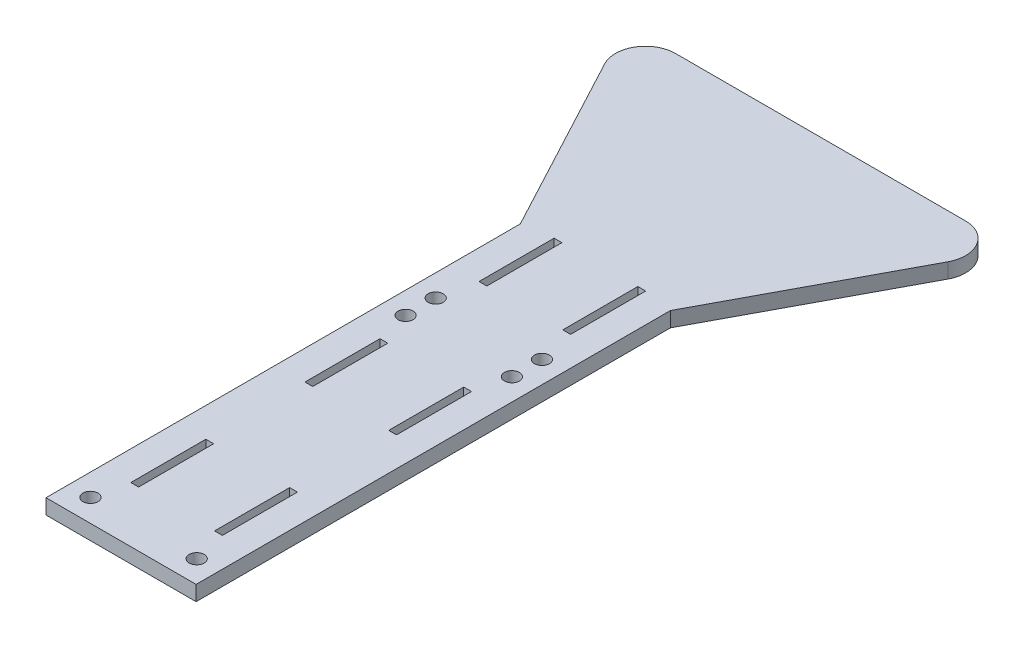
SolidWorks part; units mm, degrees
material "PC High Viscosity"
ref_plane "Front" through (0, 0, 0) normal (0, 0, 1) x (1, 0, 0)
ref_plane "Top" through (0, 0, 0) normal (0, 1, 0) x (1, 0, 0)
ref_plane "Right" through (0, 0, 0) normal (1, 0, 0) x (0, 0, -1)
sketch "Sketch1" plane through (0, 0, 0) normal (0, 1, 0) x (1, 0, 0)
  line L0 (-31.75, 0) -> (31.75, 0)
  line L1 (31.75, 0) -> (31.75, 200.66)
  line L2 (31.75, 200.66) -> (82.55, 295.91)
  line L3 (82.55, 295.91) -> (-82.55, 295.91)
  line L4 (-82.55, 295.91) -> (-31.75, 200.66)
  line L5 (-31.75, 200.66) -> (-31.75, 0)
  point P4 (0, 0)
  dimension "D1" = 63.5
  dimension "D2" = 200.66
  dimension "D3" = 95.25
  dimension "D4" = 165.1
extrude "Boss-Extrude1" add sketch "Sketch1" along normal blind 6.35
sketch "Sketch2" plane through (0, 6.35, 0) normal (0, 1, 0) x (1, 0, 0)
  line L0 (-19.304, 199.39) -> (-19.304, 173.99) construction
  line L1 (-19.304, 173.99) -> (-16.129, 173.99) construction
  line L2 (-16.129, 173.99) -> (-16.129, 199.39) construction
  line L3 (-16.129, 199.39) -> (-19.304, 199.39) construction
  line L4 (-19.304, 125.73) -> (-19.304, 100.33) construction
  line L5 (-19.304, 100.33) -> (-16.129, 100.33) construction
  line L6 (-16.129, 100.33) -> (-16.129, 125.73) construction
  line L7 (-16.129, 125.73) -> (-19.304, 125.73) construction
  line L12 (-19.304, 52.07) -> (-19.304, 26.67) construction
  line L13 (-19.304, 26.67) -> (-16.129, 26.67) construction
  line L14 (-16.129, 26.67) -> (-16.129, 52.07) construction
  line L15 (-16.129, 52.07) -> (-19.304, 52.07) construction
  line L20 (-19.304, 199.39) -> (-19.304, 173.99) construction
  line L21 (-19.304, 173.99) -> (-16.129, 173.99) construction
  line L22 (-16.129, 173.99) -> (-16.129, 199.39) construction
  line L23 (-16.129, 199.39) -> (-19.304, 199.39) construction
  line L24 (-19.304, 125.73) -> (-19.304, 100.33) construction
  line L25 (-19.304, 100.33) -> (-16.129, 100.33) construction
  line L26 (-16.129, 100.33) -> (-16.129, 125.73) construction
  line L27 (-16.129, 125.73) -> (-19.304, 125.73) construction
  line L32 (-19.304, 52.07) -> (-19.304, 26.67) construction
  line L33 (-19.304, 26.67) -> (-16.129, 26.67) construction
  line L34 (-16.129, 26.67) -> (-16.129, 52.07) construction
  line L35 (-16.129, 52.07) -> (-19.304, 52.07) construction
  line L36 (16.129, 52.07) -> (16.129, 26.67) construction
  line L37 (16.129, 26.67) -> (19.304, 26.67) construction
  line L38 (19.304, 26.67) -> (19.304, 52.07) construction
  line L39 (19.304, 52.07) -> (16.129, 52.07) construction
  line L44 (16.129, 125.73) -> (16.129, 100.33) construction
  line L45 (16.129, 100.33) -> (19.304, 100.33) construction
  line L46 (19.304, 100.33) -> (19.304, 125.73) construction
  line L47 (19.304, 125.73) -> (16.129, 125.73) construction
  line L48 (16.129, 199.39) -> (16.129, 173.99) construction
  line L49 (16.129, 173.99) -> (19.304, 173.99) construction
  line L50 (19.304, 173.99) -> (19.304, 199.39) construction
  line L51 (19.304, 199.39) -> (16.129, 199.39) construction
  line L56 (16.129, 52.07) -> (16.129, 26.67) construction
  line L57 (16.129, 26.67) -> (19.304, 26.67) construction
  line L58 (19.304, 26.67) -> (19.304, 52.07) construction
  line L59 (19.304, 52.07) -> (16.129, 52.07) construction
  line L60 (16.129, 125.73) -> (16.129, 100.33) construction
  line L61 (16.129, 100.33) -> (19.304, 100.33) construction
  line L62 (19.304, 100.33) -> (19.304, 125.73) construction
  line L63 (19.304, 125.73) -> (16.129, 125.73) construction
  line L68 (16.129, 199.39) -> (16.129, 173.99) construction
  line L69 (16.129, 173.99) -> (19.304, 173.99) construction
  line L70 (19.304, 173.99) -> (19.304, 199.39) construction
  line L71 (19.304, 199.39) -> (16.129, 199.39) construction
  line L72 (-19.3675, 23.495) -> (-19.304, 26.67) construction
  line L73 (-19.3675, 23.495) -> (-16.0655, 23.495)
  line L74 (-19.3675, 23.495) -> (-19.3675, 55.245)
  line L75 (-19.3675, 55.245) -> (-16.0655, 55.245)
  line L76 (-16.0655, 23.495) -> (-16.0655, 55.245)
  line L77 (-19.3675, 97.155) -> (-16.0655, 97.155)
  line L78 (-19.3675, 97.155) -> (-19.3675, 128.905)
  line L79 (-19.3675, 128.905) -> (-16.0655, 128.905)
  line L80 (-16.0655, 97.155) -> (-16.0655, 128.905)
  line L81 (-19.3675, 170.815) -> (-16.0655, 170.815)
  line L82 (-19.3675, 170.815) -> (-19.3675, 202.565)
  line L83 (-19.3675, 202.565) -> (-16.0655, 202.565)
  line L84 (-16.0655, 170.815) -> (-16.0655, 202.565)
  line L85 (16.0655, 23.495) -> (19.3675, 23.495)
  line L86 (16.0655, 23.495) -> (16.0655, 55.245)
  line L87 (16.0655, 55.245) -> (19.3675, 55.245)
  line L88 (19.3675, 23.495) -> (19.3675, 55.245)
  line L89 (16.0655, 97.155) -> (19.3675, 97.155)
  line L90 (16.0655, 97.155) -> (16.0655, 128.905)
  line L91 (16.0655, 128.905) -> (19.3675, 128.905)
  line L92 (19.3675, 97.155) -> (19.3675, 128.905)
  line L93 (16.0655, 170.815) -> (19.3675, 170.815)
  line L94 (16.0655, 170.815) -> (16.0655, 202.565)
  line L95 (16.0655, 202.565) -> (19.3675, 202.565)
  line L96 (19.3675, 170.815) -> (19.3675, 202.565)
  line L97 (-16.129, 52.07) -> (-16.0655, 55.245) construction
  line L98 (-19.3675, 97.155) -> (-19.304, 100.33) construction
  line L99 (-16.129, 125.73) -> (-16.0655, 128.905) construction
  line L100 (-19.304, 173.99) -> (-19.3675, 170.815) construction
  line L101 (-16.129, 199.39) -> (-16.0655, 202.565) construction
  line L102 (16.129, 199.39) -> (16.0655, 202.565) construction
  line L103 (19.304, 173.99) -> (19.3675, 170.815) construction
  line L104 (16.129, 125.73) -> (16.0655, 128.905) construction
  line L105 (19.304, 100.33) -> (19.3675, 97.155) construction
  line L106 (16.129, 52.07) -> (16.0655, 55.245) construction
  line L107 (19.304, 26.67) -> (19.3675, 23.495) construction
  dimension "D1" = 3.302
  dimension "D2" = 31.75
extrude "Cut-Extrude1" cut sketch "Sketch2" against normal through all
sketch "Sketch3" plane through (0, 6.35, 0) normal (0, 1, 0) x (1, 0, 0)
  line L0 (0, 295.91) -> (0, 149.225) construction
  line L1 (82.55, 295.91) -> (-82.55, 295.91) construction
  line L2 (0, 149.225) -> (-31.75, 149.225) construction
  line L3 (-31.75, 200.66) -> (-31.75, 0) construction
  line L6 (-19.304, 128.27) -> (-19.304, 171.45) construction
  line L9 (-31.75, 0) -> (31.75, 0) construction
  circle A0 centre (-22.479, 155.575) radius 3.175
  circle A1 centre (-22.479, 142.875) radius 3.175
  circle A2 centre (22.479, 142.875) radius 3.175
  circle A3 centre (22.479, 155.575) radius 3.175
  circle A10 centre (-22.479, 9.525) radius 3.175
  circle A12 centre (22.479, 9.525) radius 3.175
  dimension "D2" = 6.35
  dimension "D4" = 9.271
  dimension "D3" = 12.7
  dimension "D6" = 6.35
  dimension "D1" = 9.525
  dimension "D5" = 149.225
extrude "Cut-Extrude2" cut sketch "Sketch3" against normal through all
fillet "Fillet1" radius 12.7 2 edges at (82.55, 3.175, -295.91) (-82.55, 3.175, -295.91)
